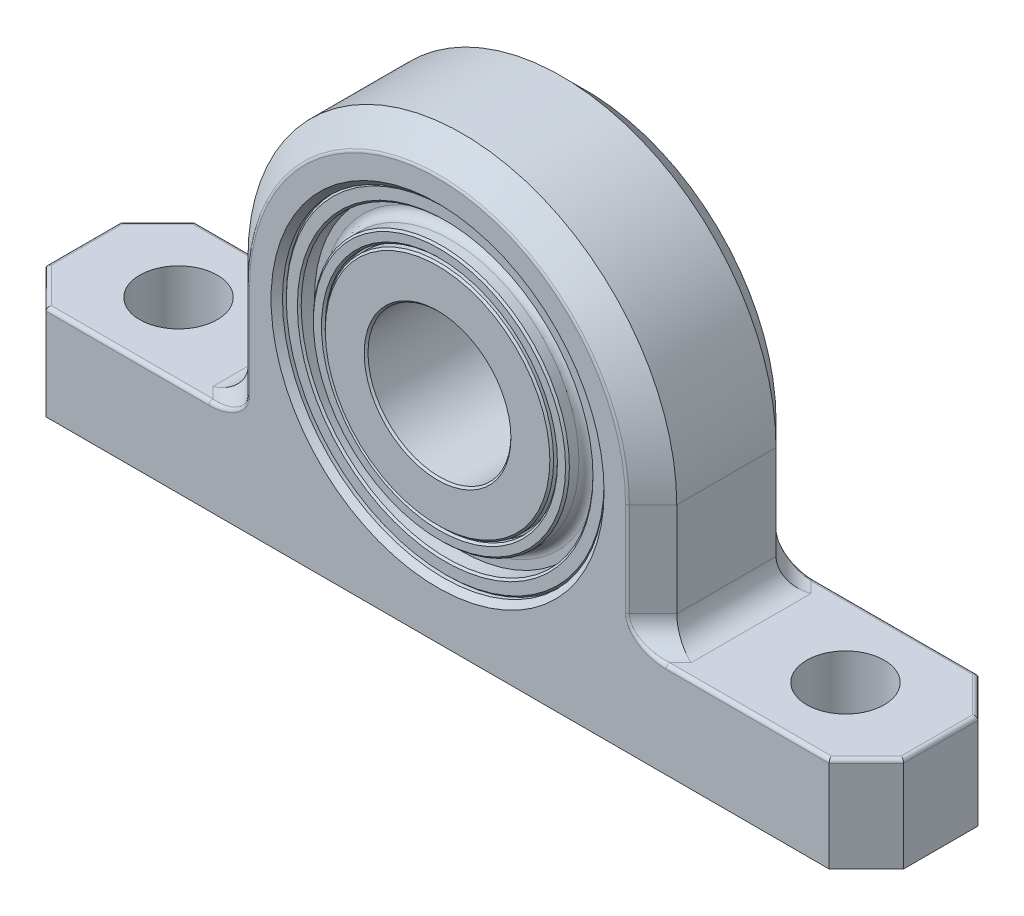
SolidWorks part; units mm, degrees
ref_plane "Front Plane" through (0, 0, 0) normal (0, 0, 1) x (1, 0, 0)
ref_plane "Top Plane" through (0, 0, 0) normal (0, 1, 0) x (1, 0, 0)
ref_plane "Right Plane" through (0, 0, 0) normal (1, 0, 0) x (0, 0, -1)
sketch "Sketch1" plane through (0, 0, 0) normal (0, 0, 1) x (1, 0, 0)
  line L0 (14.2875, 0) -> (14.2875, -7.9375)
  line L1 (14.2875, -7.9375) -> (28.575, -7.9375)
  line L2 (28.575, -7.9375) -> (28.575, -14.2875)
  line L3 (28.575, -14.2875) -> (-28.575, -14.2875)
  line L4 (-28.575, -14.2875) -> (-28.575, -7.9375)
  line L5 (-28.575, -7.9375) -> (-14.2875, -7.9375)
  line L6 (-14.2875, -7.9375) -> (-14.2875, 0)
  circle A0 centre (0, 0) radius 4.7625
  arc A1 (14.2875, 0) -> (-14.2875, 0) centre (0, 0) ccw
  circle A2 centre (0, 0) radius 10.7156
  point P12 (0, 10.7156)
  point P13 (0, 4.7625)
  dimension "shaft dia" = 9.525
  dimension "D1" = 21.4312
sketch "Sketch2" plane through (0, 0, 0) normal (0, 1, 0) x (1, 0, 0)
  line L0 (0, 4.9609) -> (0, -4.9609) construction
  line L1 (-22.225, 0) -> (22.225, 0) construction
  circle A0 centre (22.225, 0) radius 2.5797
  circle A1 centre (-22.225, 0) radius 2.5797
  dimension "Overall Width" = 9.9219
sketch "Sketch3" plane through (0, 0, 0) normal (0, 0, 1) x (1, 0, 0)
  line L0 (14.2875, 0) -> (14.2875, -7.9375) construction
  line L1 (28.575, -7.9375) -> (28.575, -14.2875) construction
  line L2 (14.2875, -7.9375) -> (28.575, -7.9375) construction
  line L3 (28.575, -14.2875) -> (-28.575, -14.2875) construction
  line L4 (-28.575, -14.2875) -> (-28.575, -7.9375) construction
  line L5 (-28.575, -7.9375) -> (-14.2875, -7.9375) construction
  line L6 (-14.2875, -7.9375) -> (-14.2875, 0) construction
  line L7 (14.2875, 0) -> (14.2875, -7.9375)
  line L8 (28.575, -7.9375) -> (28.575, -14.2875)
  line L9 (14.2875, -7.9375) -> (28.575, -7.9375)
  line L10 (28.575, -14.2875) -> (-28.575, -14.2875)
  line L11 (-28.575, -14.2875) -> (-28.575, -7.9375)
  line L12 (-28.575, -7.9375) -> (-14.2875, -7.9375)
  line L13 (-14.2875, -7.9375) -> (-14.2875, 0)
  arc A0 (14.2875, 0) -> (-14.2875, 0) centre (0, 0) ccw construction
  circle A1 centre (0, 0) radius 10.7156 construction
  arc A2 (14.2875, 0) -> (-14.2875, 0) centre (0, 0) ccw
  circle A3 centre (0, 0) radius 10.7156
extrude "Extrude1" add sketch "Sketch3" along normal up to vertex (4.9609 mm away) and the other way up to vertex (4.9609 mm away) up to point (0, 0, 4.9609) other way up to point (0, 0, -4.9609)
sketch "Sketch4" plane through (0, -7.9375, 0) normal (0, 1, 0) x (1, 0, 0)
  line L0 (-28.575, 4.9609) -> (-28.575, 2.4805)
  line L1 (-28.575, -4.9609) -> (-28.575, 4.9609) construction
  line L2 (-28.575, 2.4805) -> (-26.0945, 4.9609)
  line L3 (-14.2875, 4.9609) -> (-28.575, 4.9609) construction
  line L4 (-26.0945, 4.9609) -> (-28.575, 4.9609)
  line L5 (0, 0) -> (0, 4.9609) construction
  line L6 (0, 0) -> (-22.225, 0) construction
  line L7 (26.0945, 4.9609) -> (28.575, 4.9609)
  line L8 (28.575, 2.4805) -> (26.0945, 4.9609)
  line L9 (28.575, 4.9609) -> (28.575, 2.4805)
  line L10 (28.575, -4.9609) -> (28.575, -2.4805)
  line L11 (28.575, -2.4805) -> (26.0945, -4.9609)
  line L12 (26.0945, -4.9609) -> (28.575, -4.9609)
  line L13 (-26.0945, -4.9609) -> (-28.575, -4.9609)
  line L14 (-28.575, -2.4805) -> (-26.0945, -4.9609)
  line L15 (-28.575, -4.9609) -> (-28.575, -2.4805)
  circle A0 centre (-22.225, 0) radius 2.5797 construction
  circle A1 centre (22.225, 0) radius 2.5797 construction
  circle A2 centre (-22.225, 0) radius 2.5797
  circle A3 centre (22.225, 0) radius 2.5797
  dimension "D1" = 45
  dimension "D2" = 2.4805
extrude "Cut-Extrude1" cut sketch "Sketch4" against normal through all
chamfer "Chamfer3" distance 1.6536 angle 45 6 edges at (-14.2875, -3.9687, -4.9609) (0, 14.2875, -4.9609) (14.2875, -3.9687, -4.9609) (-14.2875, -3.9687, 4.9609) (0, 14.2875, 4.9609) (14.2875, -3.9687, 4.9609)
fillet "Fillet6" radius 1.6536 6 edges at (14.2875, -7.9375, 0) (13.4607, -7.9375, -4.1341) (13.4607, -7.9375, 4.1341) (-13.4607, -7.9375, -4.1341) (-13.4607, -7.9375, 4.1341) (-14.2875, -7.9375, 0)
fillet "Fillet7" radius 0.254 20 edges at (20.5335, -7.9375, -4.9609) (13.3188, -7.4532, -4.9609) (12.6339, -3.1419, -4.9609) (0, 12.6339, -4.9609) (-12.6339, -3.1419, -4.9609) (-13.3188, -7.4532, -4.9609) (20.5335, -7.9375, 4.9609) (13.3188, -7.4532, 4.9609) (12.6339, -3.1419, 4.9609) (0, 12.6339, 4.9609) (-12.6339, -3.1419, 4.9609) (-13.3188, -7.4532, 4.9609) (27.3348, -7.9375, 3.7207) (28.575, -7.9375, 0) (27.3348, -7.9375, -3.7207) (-20.5335, -7.9375, -4.9609) (-27.3348, -7.9375, -3.7207) (-28.575, -7.9375, 0) (-27.3348, -7.9375, 3.7207) (-20.5335, -7.9375, 4.9609)
chamfer "Chamfer4" distance 0.381 angle 45 2 edges at (10.7156, 0, -4.9609) (10.7156, 0, 4.9609)
sketch "Sketch5" plane through (0, 0, 0) normal (1, 0, 0) x (0, 0, -1)
  line L0 (-4.4529, 9.7234) -> (-3.4369, 9.7234)
  line L1 (0, 10.7156) -> (0, 4.7625) construction
  line L2 (4.4529, 10.7156) -> (4.4529, 9.7234)
  line L4 (4.4529, 9.7234) -> (3.4369, 9.7234)
  line L5 (-3.4369, 9.7234) -> (-3.4369, 8.5328)
  line L6 (-3.4369, 8.5328) -> (-4.8339, 8.5328)
  line L7 (-4.3259, 7.6121) -> (-4.3259, 7.7391)
  line L8 (-4.9609, 4.7625) -> (4.9609, 4.7625)
  line L9 (-4.3259, 7.6121) -> (-4.9609, 7.6121)
  line L10 (-4.4529, 10.7156) -> (4.4529, 10.7156)
  line L11 (3.4369, 9.7234) -> (3.4369, 8.5328)
  line L12 (-4.9609, 7.6121) -> (-4.9609, 4.7625)
  line L13 (-4.4529, 10.7156) -> (-4.4529, 9.7234)
  line L15 (-4.3259, 7.7391) -> (-4.8339, 7.7391)
  line L16 (-4.8339, 7.7391) -> (-4.8339, 8.5328)
  line L17 (0, 10.7156) -> (0, 14.2875) construction
  line L18 (0, 14.2875) -> (0, 0) construction
  line L19 (3.4369, 8.5328) -> (4.8339, 8.5328)
  line L20 (4.8339, 7.7391) -> (4.8339, 8.5328)
  line L21 (4.3259, 7.7391) -> (4.8339, 7.7391)
  line L22 (4.3259, 7.6121) -> (4.3259, 7.7391)
  line L23 (4.3259, 7.6121) -> (4.9609, 7.6121)
  line L24 (4.9609, 7.6121) -> (4.9609, 4.7625)
  line L27 (3.3073, 14.2875) -> (-3.3073, 14.2875) construction
  point P9 (0, 7.7391)
  dimension "D1" = 5.9531
  dimension "D2" = 0.9922
  dimension "D3" = 1.1906
  dimension "D6" = 1.016
  dimension "D5" = 0.635
  dimension "D7" = 0.127
  dimension "D8" = 0.127
  dimension "D9" = 0.508
revolve "Revolve1" add sketch "Sketch5" angle 360 about L0
chamfer "Chamfer5" distance 0.127 angle 45 12 edges at (-7.6121, 0, 4.9609) (-4.7625, 0, 4.9609) (-8.5328, 0, 4.8339) (-7.7391, 0, 4.8339) (-10.7156, 0, 4.4529) (-9.7234, 0, 4.4529) (-4.7625, 0, -4.9609) (-7.6121, 0, -4.9609) (-7.7391, 0, -4.8339) (-8.5328, 0, -4.8339) (-9.7234, 0, -4.4529) (-10.7156, 0, -4.4529)
fillet "Fillet8" radius 0.635 2 edges at (-8.5328, 0, 3.4369) (-8.5328, 0, -3.4369)
equation "\"D1@Sketch1\"=\"I@Sketch1\"*.75"
equation "\"D2@Sketch4\" = \"Overall Width@Sketch2\" / 4"
equation "\"D1@Chamfer3\" = \"Overall Width@Sketch2\" / 6"
equation "\"D1@Fillet6\"=\"D1@Chamfer3\""
equation "\"D2@Sketch5\"=\"D1@Sketch5\"/6"
equation "\"D3@Sketch5\"=\"D2@Sketch5\"*1.2"
